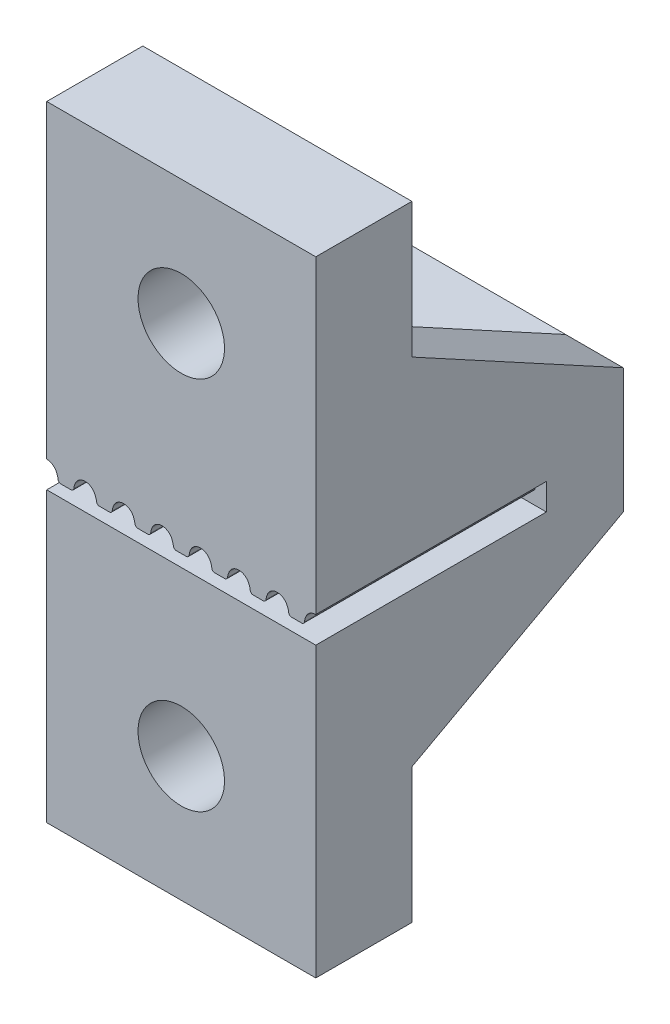
SolidWorks part; units mm, degrees
material "ABS"
ref_plane "Front Plane" through (0, 0, 0) normal (0, 0, 1) x (1, 0, 0)
ref_plane "Top Plane" through (0, 0, 0) normal (0, 1, 0) x (1, 0, 0)
ref_plane "Right Plane" through (0, 0, 0) normal (1, 0, 0) x (0, 0, -1)
sketch "Sketch3" plane through (0, 0, 0) normal (0, 0, 1) x (1, 0, 0)
  line L1 (0, -2) -> (14, -2)
  line L2 (0, -2) -> (0, 4.5)
  line L3 (0, 4.5) -> (14, 4.5)
  line L4 (14, -2) -> (14, 4.5)
  dimension "D1" = 14
  dimension "D2" = 6.5
  dimension "D3" = 2
extrude "Boss-Extrude2" add sketch "Sketch3" along normal blind 16
sketch "Sketch1" plane through (0, 0, 0) normal (0, 0, 1) x (1, 0, 0)
  line L4 (1, 0.63) -> (1, 1.38) construction
  line L5 (0.7402, 0.63) -> (1.2598, 0.63)
  line L6 (2, 1.38) -> (2, 0)
  line L9 (0, 1.38) -> (0, 0)
  line L10 (0, 0) -> (2, 0)
  arc A0 (1.2598, 0.63) -> (1.4085, 0.7604) centre (1.2598, 0.78) ccw
  arc A1 (1.4085, 0.7604) -> (1.5011, 1.0682) centre (2.4, 0.63) cw
  arc A2 (1.5011, 1.0682) -> (2, 1.38) centre (2, 0.825) cw
  arc A3 (0.4989, 1.0682) -> (0, 1.38) centre (0, 0.825) ccw
  arc A4 (0.5915, 0.7604) -> (0.4989, 1.0682) centre (-0.4, 0.63) ccw
  arc A5 (0.7402, 0.63) -> (0.5915, 0.7604) centre (0.7402, 0.78) cw
  dimension "D1" = 0.555
  dimension "D2" = 1
  dimension "D3" = 0.15
  dimension "D4" = 0.4
  dimension "D5" = 0.75
  dimension "D6" = 2
  dimension "D7" = 1.38
extrude "Cut-Extrude1" cut sketch "Sketch1" along normal blind 19 from offset 4
pattern_linear "LPattern2" count 7 spacing 2 along (1, 0, 0) of "Cut-Extrude1"
sketch "Sketch4" plane through (0, 4.5, 16) normal (0, 0, -1) x (-1, 0, 0)
  line L0 (0, -6.5) -> (-14, -6.5) construction
  line L1 (-7, -13) -> (0, -13) construction
  line L2 (-14, -6.5) -> (-14, -19.5)
  line L3 (-14, -19.5) -> (0, -19.5)
  line L4 (0, -6.5) -> (0, -19.5)
  line L5 (-14, -6.5) -> (-14, 0) construction
  line L6 (-14, -6.5) -> (-14, -4.5) construction
  line L7 (0, 0) -> (-14, 0)
  line L8 (-14, 6.5) -> (0, 6.5) construction
  line L9 (0, -4.5) -> (0, -6.5) construction
  line L10 (-7, -13) -> (-7, 6.5) construction
  line L11 (0, 0) -> (0, 13)
  line L12 (0, 13) -> (-14, 13)
  line L13 (-14, -6.5) -> (0, -6.5)
  line L14 (-14, 0) -> (-14, 13)
  circle A0 centre (-7, 6.5) radius 2.25
  circle A1 centre (-7, -13) radius 2.25
  point P23 (-7, -6.5)
  dimension "D5" = 4.5
  dimension "D1" = 13
extrude "Boss-Extrude3" add sketch "Sketch4" along normal blind 5
sketch "Sketch6" plane through (0, 4.5, 0) normal (0, 1, 0) x (1, 0, 0)
  line L1 (0, -18) -> (14, -18)
  line L2 (0, -18) -> (0, -14)
  line L3 (0, -14) -> (14, -14)
  line L4 (14, -18) -> (14, -14)
  dimension "D1" = 4
extrude "Cut-Extrude3" [suppressed] cut sketch "Sketch6" against normal up to vertex
sketch "Sketch7" plane through (0, 0, 0) normal (-1, 0, 0) x (0, 0, 1)
  line L0 (0, -2) -> (11, -7.9828)
  line L1 (11, -7.9828) -> (11, -2)
  line L2 (11, -2) -> (0, -2)
  line L3 (11, -15) -> (11, -2) construction
extrude "Boss-Extrude4" add sketch "Sketch7" against normal blind 3
extrude "Boss-Extrude5" add sketch "Sketch7<2>" against normal blind 3 from offset 11 offset against normal yes
sketch "Sketch7<2>" plane through (0, 0, 0) normal (-1, 0, 0) x (0, 0, 1) same geometry as "Sketch7"
sketch "Sketch5" plane through (0, 0, 11) normal (0, 0, -1) x (-1, 0, 0)
  circle A0 centre (-7, 11) radius 4.5
  circle A1 centre (-7, -8.5) radius 4.5
  dimension "D1" = 9
extrude "Cut-Extrude2" cut sketch "Sketch5" against normal blind 0.1 and the other way blind 10
ref_plane "Plane1" through (0, 1.25, 0) normal (0, 1, 0) x (1, 0, 0)
mirror "Mirror1" about plane through (0, 1.25, 0) normal (0, 1, 0) of "Cut-Extrude2", "Boss-Extrude5", "Boss-Extrude4"
